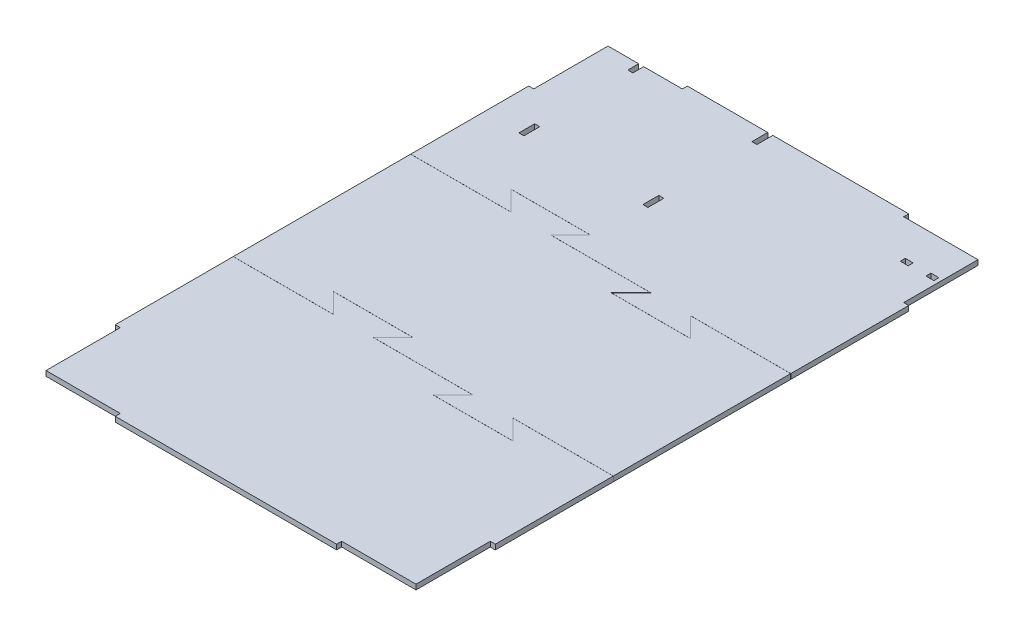
SolidWorks part; units mm, degrees
ref_plane "Front Plane" through (0, 0, 0) normal (0, 0, 1) x (1, 0, 0)
ref_plane "Top Plane" through (0, 0, 0) normal (0, 1, 0) x (1, 0, 0)
ref_plane "Right Plane" through (0, 0, 0) normal (1, 0, 0) x (0, 0, -1)
sketch "Sketch1" plane through (0, 0, 0) normal (0, 1, 0) x (1, 0, 0)
  line L7 (-239.5, -360.5) -> (239.5, -360.5)
  line L8 (-239.5, -360.5) -> (-239.5, 360.5)
  line L9 (-239.5, 360.5) -> (239.5, 360.5)
  line L10 (239.5, -360.5) -> (239.5, 360.5)
  point P0 (0, 0)
  point P3 (239.5, 0)
  point P6 (0, 0)
  point P11 (0, -360.5)
  dimension "D1" = 721
  dimension "D2" = 479
extrude "Boss-Extrude1" add sketch "Sketch1" along normal mid plane 6.35
sketch "Sketch2" plane through (0, 3.175, 0) normal (0, 1, 0) x (1, 0, 0)
  line L0 (-239.5, 360.5) -> (-239.5, 260.5)
  line L1 (-239.5, 360.5) -> (-239.5, -360.5) construction
  line L2 (-239.5, 260.5) -> (-233.15, 260.5)
  line L3 (-233.15, 260.5) -> (-233.15, 354.15)
  line L4 (-233.15, 354.15) -> (-139.5, 354.15)
  line L5 (-139.5, 354.15) -> (-139.5, 360.5)
  line L6 (239.5, 360.5) -> (-239.5, 360.5) construction
  line L7 (-139.5, 360.5) -> (-239.5, 360.5)
  line L8 (239.5, 360.5) -> (139.5, 360.5)
  line L9 (139.5, 360.5) -> (139.5, 354.15)
  line L10 (139.5, 354.15) -> (233.15, 354.15)
  line L11 (233.15, 354.15) -> (233.15, 260.5)
  line L12 (233.15, 260.5) -> (239.5, 260.5)
  line L13 (239.5, -360.5) -> (239.5, 360.5) construction
  line L14 (239.5, 260.5) -> (239.5, 360.5)
  line L15 (239.5, -360.5) -> (239.5, -260.5)
  line L16 (239.5, -260.5) -> (233.15, -260.5)
  line L17 (233.15, -260.5) -> (233.15, -354.15)
  line L18 (233.15, -354.15) -> (139.5, -354.15)
  line L19 (139.5, -354.15) -> (139.5, -360.5)
  line L20 (-239.5, -360.5) -> (239.5, -360.5) construction
  line L21 (139.5, -360.5) -> (239.5, -360.5)
  line L22 (-239.5, -360.5) -> (-139.5, -360.5)
  line L23 (-139.5, -360.5) -> (-139.5, -354.15)
  line L24 (-139.5, -354.15) -> (-233.15, -354.15)
  line L25 (-233.15, -354.15) -> (-233.15, -260.5)
  line L26 (-233.15, -260.5) -> (-239.5, -260.5)
  line L27 (-239.5, -260.5) -> (-239.5, -360.5)
  dimension "D1" = 100
  dimension "D2" = 6.35
extrude "Cut-Extrude1" cut sketch "Sketch2" against normal through all
sketch "Sketch3" plane through (0, -3.175, 0) normal (0, -1, 0) x (1, 0, 0)
  line L0 (233.15, -354.15) -> (233.15, -260.5) construction
  line L1 (139.5, -354.15) -> (233.15, -354.15) construction
  line L2 (139.5, -360.5) -> (-139.5, -360.5) construction
  line L3 (-31.8, -360.5) -> (-38.15, -360.5)
  line L4 (-31.8, -360.5) -> (-31.8, -340.5)
  line L5 (-31.8, -340.5) -> (-38.15, -340.5)
  line L6 (-38.15, -360.5) -> (-38.15, -340.5)
  line L7 (-233.15, -260.5) -> (-233.15, -354.15) construction
  line L8 (185.85, -303.45) -> (195.85, -303.45)
  line L9 (185.85, -303.45) -> (185.85, -309.8)
  line L10 (185.85, -309.8) -> (195.85, -309.8)
  line L11 (195.85, -303.45) -> (195.85, -309.8)
  line L12 (228.15, -303.45) -> (228.15, -309.8)
  line L13 (218.15, -303.45) -> (228.15, -303.45)
  line L14 (218.15, -303.45) -> (218.15, -309.8)
  line L15 (218.15, -309.8) -> (228.15, -309.8)
  line L16 (-188.15, -360.5) -> (-194.5, -360.5)
  line L17 (-188.15, -360.5) -> (-188.15, -340.5)
  line L18 (-188.15, -340.5) -> (-194.5, -340.5)
  line L19 (-194.5, -360.5) -> (-194.5, -340.5)
  line L20 (-31.8, -223.15) -> (-38.15, -223.15)
  line L21 (-31.8, -223.15) -> (-31.8, -203.15)
  line L22 (-31.8, -203.15) -> (-38.15, -203.15)
  line L23 (-38.15, -223.15) -> (-38.15, -203.15)
  line L24 (-188.15, -223.15) -> (-194.5, -223.15)
  line L25 (-188.15, -223.15) -> (-188.15, -203.15)
  line L26 (-188.15, -203.15) -> (-194.5, -203.15)
  line L27 (-194.5, -223.15) -> (-194.5, -203.15)
  dimension "D1" = 10
  dimension "D2" = 6.35
  dimension "D3" = 5
  dimension "D4" = 42.3
  dimension "D5" = 44.35
  dimension "D6" = 6.35
  dimension "D7" = 20
  dimension "D8" = 117.35
  dimension "D9" = 150
  dimension "D10" = 45
extrude "Cut-Extrude2" cut sketch "Sketch3" against normal through all
sketch "Sketch4" plane through (0, 3.175, 0) normal (0, 1, 0) x (1, 0, 0)
  line L0 (-239.5, -111.7667) -> (-113.1667, -111.7667)
  line L1 (-239.5, 111.8667) -> (-113.1667, 111.8667)
  line L2 (-239.5, 260.5) -> (-239.5, -260.5) construction
  line L3 (-113.1667, -111.7667) -> (-138.1667, -86.7667)
  line L4 (-138.1667, -86.7667) -> (-38.1667, -86.7667)
  line L5 (-38.1667, -86.7667) -> (-63.1667, -111.7667)
  line L6 (-63.1667, -111.7667) -> (63.1667, -111.7667)
  line L7 (63.1667, -111.7667) -> (38.1667, -136.7667)
  line L8 (38.1667, -136.7667) -> (138.1667, -136.7667)
  line L9 (138.1667, -136.7667) -> (113.1667, -111.7667)
  line L10 (113.1667, -111.7667) -> (239.5, -111.7667)
  line L11 (-113.1667, 111.8667) -> (-138.1667, 136.8667)
  line L12 (239.5, -260.5) -> (239.5, 260.5) construction
  line L14 (-239.5, -111.8667) -> (-112.9252, -111.8667)
  line L15 (-112.9252, -111.8667) -> (-137.9252, -86.8667)
  line L16 (-137.9252, -86.8667) -> (-38.4081, -86.8667)
  line L17 (-38.4081, -86.8667) -> (-63.4081, -111.8667)
  line L18 (-63.4081, -111.8667) -> (62.9252, -111.8667)
  line L19 (62.9252, -111.8667) -> (37.9252, -136.8667)
  line L20 (37.9252, -136.8667) -> (138.4081, -136.8667)
  line L21 (138.4081, -136.8667) -> (113.4081, -111.8667)
  line L22 (113.4081, -111.8667) -> (239.5, -111.8667)
  line L23 (-239.5, -111.8667) -> (-239.5, -111.7667)
  line L24 (239.5, -111.8667) -> (239.5, -111.7667)
  line L25 (-138.1667, 136.8667) -> (-38.1667, 136.8667)
  line L26 (-38.1667, 136.8667) -> (-63.1667, 111.8667)
  line L27 (-63.1667, 111.8667) -> (63.1667, 111.8667)
  line L28 (63.1667, 111.8667) -> (38.1667, 86.8667)
  line L29 (38.1667, 86.8667) -> (138.1667, 86.8667)
  line L30 (138.1667, 86.8667) -> (113.1667, 111.8667)
  line L31 (113.1667, 111.8667) -> (239.5, 111.8667)
  line L32 (-239.5, 111.7667) -> (-112.9252, 111.7667)
  line L33 (-112.9252, 111.7667) -> (-137.9252, 136.7667)
  line L34 (-137.9252, 136.7667) -> (-38.4081, 136.7667)
  line L35 (-38.4081, 136.7667) -> (-63.4081, 111.7667)
  line L36 (-63.4081, 111.7667) -> (62.9252, 111.7667)
  line L37 (62.9252, 111.7667) -> (37.9252, 86.7667)
  line L38 (37.9252, 86.7667) -> (138.4081, 86.7667)
  line L39 (138.4081, 86.7667) -> (113.4081, 111.7667)
  line L40 (113.4081, 111.7667) -> (239.5, 111.7667)
  line L41 (-239.5, 111.7667) -> (-239.5, 111.8667)
  line L42 (239.5, 111.7667) -> (239.5, 111.8667)
  line L43 (-239.5, -111.7667) -> (-239.5, 111.8667) construction
  line L45 (0, -86.7667) -> (0, -360.5) construction
  line L47 (-139.5, -360.5) -> (139.5, -360.5) construction
  line L48 (0, -136.8667) -> (0, 136.8667) construction
  line L49 (0, 86.7667) -> (0, 360.5) construction
  line L50 (139.5, 360.5) -> (-31.8, 360.5) construction
  dimension "D1" = 100
  dimension "D2" = 25
  dimension "D5" = 2
  dimension "D4" = 0.1
extrude "Cut-Extrude3" cut sketch "Sketch4" against normal through all
